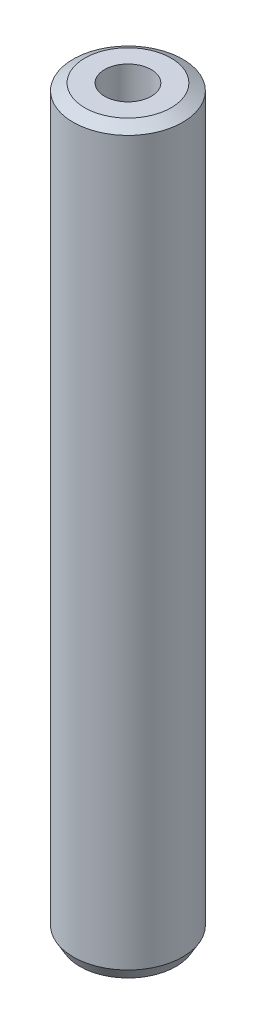
SolidWorks part; units mm, degrees
ref_plane "Front Plane" through (0, 0, 0) normal (0, 0, 1) x (1, 0, 0)
ref_plane "Top Plane" through (0, 0, 0) normal (0, 1, 0) x (1, 0, 0)
ref_plane "Right Plane" through (0, 0, 0) normal (1, 0, 0) x (0, 0, -1)
sketch "Sketch1" plane through (0, 0, 0) normal (0, 1, 0) x (1, 0, 0)
  circle A0 centre (0, 0) radius 10
  dimension "SHAFT_OD" = 20
extrude "Boss-Extrude1" add sketch "Sketch1" along normal blind 135.3421
sketch "Sketch2" plane through (0, 0, 0) normal (0, 1, 0) x (1, 0, 0)
  circle A0 centre (0, 0) radius 4.2469
  dimension "BORE_D" = 8.4938
extrude "Cut-Extrude1" cut sketch "Sketch2" along normal through all
chamfer "Chamfer1" distance 1.2297 angle 60 2 edges at (0, 135.3421, 10) (0, 0, 10) first distance on face at (0, 135.3421, 10) first distance on face at (0, 0, 4.2469)
